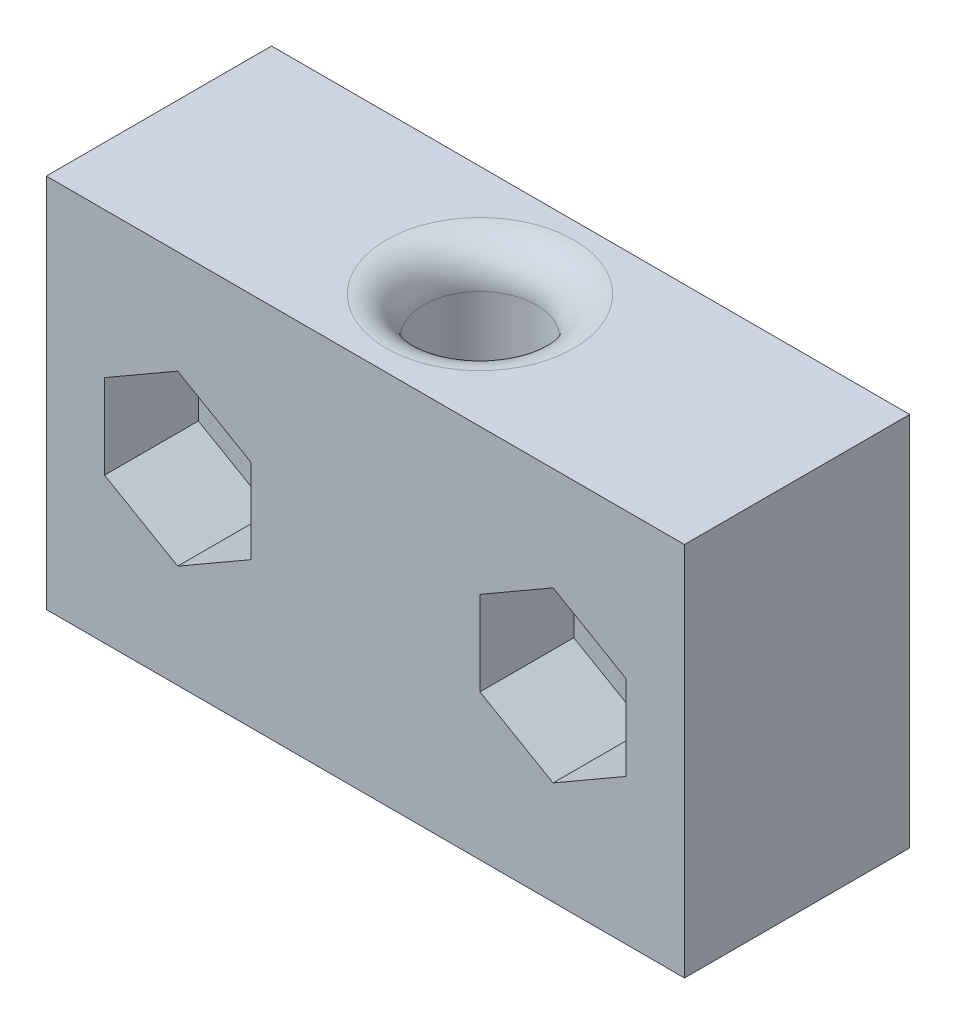
SolidWorks part; units mm, degrees
ref_plane "Front Plane" through (0, 0, 0) normal (0, 0, 1) x (1, 0, 0)
ref_plane "Top Plane" through (0, 0, 0) normal (0, 1, 0) x (1, 0, 0)
ref_plane "Right Plane" through (0, 0, 0) normal (1, 0, 0) x (0, 0, -1)
sketch "Sketch1" plane through (0, 0, 0) normal (0, 0, 1) x (1, 0, 0)
  line L1 (-17, -10) -> (17, -10)
  line L2 (-17, -10) -> (-17, 10)
  line L3 (-17, 10) -> (17, 10)
  line L4 (17, -10) -> (17, 10)
  line L5 (-17, -10) -> (17, 10) construction
  line L6 (-17, 10) -> (17, -10) construction
  point P0 (0, 0)
  dimension "D1" = 34
  dimension "D2" = 20
extrude "Boss-Extrude1" add sketch "Sketch1" along normal blind 12
sketch "Sketch2" plane through (0, 0, 0) normal (0, 0, -1) x (-1, 0, 0)
  line L0 (6.6, 0) -> (-6.6, 0) construction
  line L1 (0, -997.2319) -> (0, 49002.7681) construction
  line L3 (17, 10) -> (17, -10) construction
  circle A0 centre (10, 0) radius 4.3
  circle A1 centre (-10, 0) radius 4.3
  circle A2 centre (10, 0) radius 2.5
  circle A3 centre (-10, 0) radius 2.5
  dimension "D2" = 8.6
  dimension "D3" = 5
  dimension "D1" = 7
extrude "Cut-Extrude5" cut sketch "Sketch2" along direction (0, 0, -1) on the side against the normal up to surface (12 mm away) from surface contours A2 | A3 up to face at (0, 0, 12) starting at face at (0, 0, 0)
extrude "Cut-Extrude6" cut sketch "Sketch2<8>" against normal blind 2 from surface starting at face at (-12.5, 0, 0)
sketch "Sketch2<8>" plane through (0, 0, 0) normal (0, 0, -1) x (-1, 0, 0) same geometry as "Sketch2"
sketch "Sketch6" plane through (0, 10, 0) normal (0, 1, 0) x (1, 0, 0)
  line L0 (0, -6.6) -> (0, 6.6) construction
  circle A0 centre (0, -5.8925) radius 5
  circle A1 centre (0, -5.8925) radius 3
  dimension "D1" = 10
  dimension "D2" = 6
extrude "Cut-Extrude7" cut sketch "Sketch6" against normal up to surface (20 mm away) contours A1 up to face at (0, -10, 6)
fillet "Fillet1" radius 2 2 edges at (0, 10, 8.8925) (0, -10, 8.8925)
sketch "Sketch7" plane through (0, 0, 12) normal (0, 0, 1) x (1, 0, 0)
  line L0 (0, -990.9431) -> (0, 49009.0569) construction
  line L1 (-10, 4.5) -> (-13.8971, 2.25)
  line L2 (-13.8971, 2.25) -> (-13.8971, -2.25)
  line L3 (-13.8971, -2.25) -> (-10, -4.5)
  line L4 (-10, -4.5) -> (-6.1029, -2.25)
  line L5 (-6.1029, -2.25) -> (-6.1029, 2.25)
  line L6 (-6.1029, 2.25) -> (-10, 4.5)
  line L7 (10, 4.5) -> (6.1029, 2.25)
  line L8 (6.1029, 2.25) -> (6.1029, -2.25)
  line L9 (6.1029, -2.25) -> (10, -4.5)
  line L10 (10, -4.5) -> (13.8971, -2.25)
  line L11 (13.8971, -2.25) -> (13.8971, 2.25)
  line L12 (13.8971, 2.25) -> (10, 4.5)
  circle A0 centre (-10, 0) radius 3.8971 construction
  circle A1 centre (10, 0) radius 3.8971 construction
  dimension "D1" = 4.5
extrude "Cut-Extrude8" cut sketch "Sketch7" against normal blind 5
